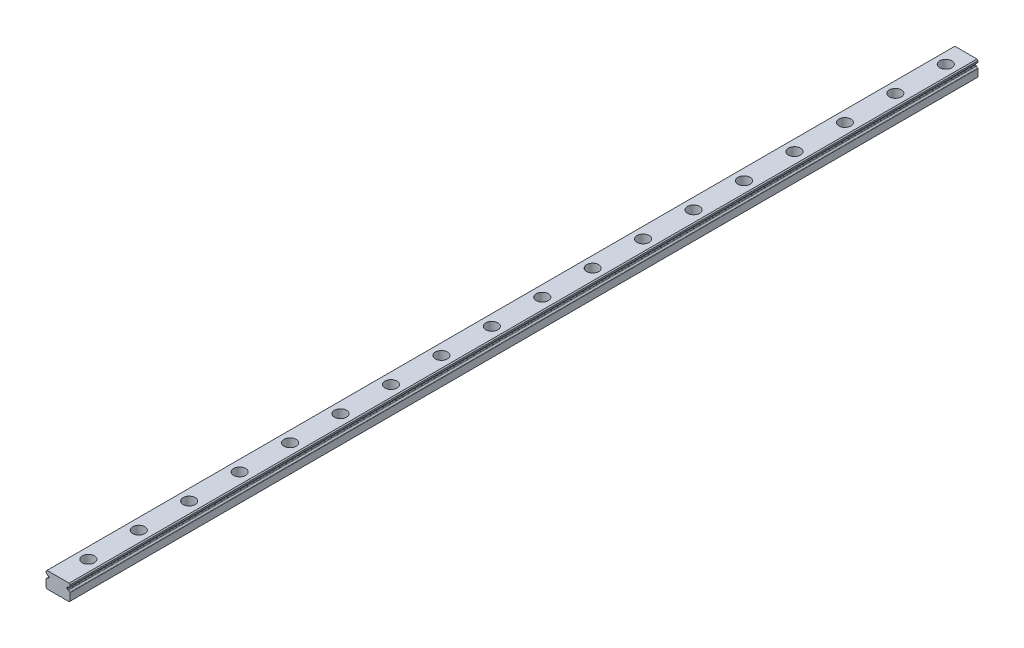
SolidWorks part; units mm, degrees
ref_plane "Płaszczyzna przednia" through (0, 0, 0) normal (0, 0, 1) x (1, 0, 0)
ref_plane "Płaszczyzna górna" through (0, 0, 0) normal (0, 1, 0) x (1, 0, 0)
ref_plane "Płaszczyzna prawa" through (0, 0, 0) normal (1, 0, 0) x (0, 0, -1)
ref_plane "Płaszczyzna1" through (0, 0, -250) normal (0, 0, -1) x (-1, 0, 0)
sketch "Szkic1" plane through (0, 0, -250) normal (0, 0, -1) x (-1, 0, 0)
  line L0 (4.4868, 0.454) -> (5.9823, 0.5848)
  line L1 (5.9823, 0.5848) -> (5.9823, 2.0015)
  line L2 (5.9823, 2.0015) -> (5.4838, 2.5)
  line L3 (5.4838, 2.5) -> (-5.4838, 2.5)
  line L4 (-5.4838, 2.5) -> (-5.9823, 2.0015)
  line L5 (-5.9823, 2.0015) -> (-5.9823, 0.5848)
  line L6 (-5.9823, 0.5848) -> (-4.4868, 0.454)
  line L7 (-4.4868, 0.454) -> (-4.4868, -0.454)
  line L8 (-4.4868, -0.454) -> (-5.9823, -0.5848)
  line L9 (-5.9823, -0.5848) -> (-5.9823, -5.5)
  line L10 (-5.9823, -5.5) -> (5.9823, -5.5)
  line L11 (5.9823, -5.5) -> (5.9823, -1.1747)
  line L12 (5.1943, -0.5159) -> (4.4868, -0.454)
  line L13 (4.4868, -0.454) -> (4.4868, 0.454)
  arc A0 (5.9823, -1.1747) -> (5.1943, -0.5159) centre (6.2815, -0.0162) cw
extrude "Dodanie-wyciągnięcie1" add sketch "Szkic1" against normal blind 450
sketch "Szkic2" plane through (0, 0, -250) normal (0, 0, -1) x (-1, 0, 0)
  line L0 (-2.3929, -5.5) -> (-1.5953, -5.5)
  arc A0 (-1.5953, -5.5) -> (-2.3929, -5.5) centre (-1.9941, -5.7991) ccw
extrude "Wytnij-wyciągnięcie1" cut sketch "Szkic2" against normal blind 500
sketch "Szkic3" plane through (0, 0, -250) normal (0, 0, -1) x (-1, 0, 0)
  line L0 (-5.1972, -0.5161) -> (-5.9823, -0.5848)
  line L1 (-5.9823, -0.5848) -> (-5.9823, -1.1927)
  arc A0 (-5.9823, -1.1927) -> (-5.1972, -0.5161) centre (-6.2938, -0.0375) ccw
extrude "Wytnij-wyciągnięcie2" cut sketch "Szkic3" against normal through all
sketch "Szkic4" plane through (0, 0, -250) normal (0, 0, -1) x (-1, 0, 0)
  line L0 (-5.9823, 1.1423) -> (-5.9823, 0.5848)
  line L1 (-5.9823, 0.5848) -> (-5.2105, 0.5173)
  arc A0 (-5.2105, 0.5173) -> (-5.9823, 1.1423) centre (-6.2815, -0.0162) ccw
extrude "Wytnij-wyciągnięcie3" cut sketch "Szkic4" against normal through all
sketch "Szkic5" plane through (0, 0, 200) normal (0, 0, 1) x (1, 0, 0)
  line L0 (-5.9823, 0.5848) -> (-5.2105, 0.5173)
  line L1 (-5.9823, 1.1423) -> (-5.9823, 0.5848)
  arc A0 (-5.2105, 0.5173) -> (-5.9823, 1.1423) centre (-6.2815, -0.0162) ccw
extrude "Wytnij-wyciągnięcie4" cut sketch "Szkic5" against normal through all
hole_wizard "Pogłębienie walcowe pod M3 Wkręt do części metalowych z łbem sześciokątnym1" positions "Szkic7" profile "Szkic6" counterbore size "M3" standard "Ansi Metric" end condition through all
sketch "Szkic7" plane through (0, 2.5, 0) normal (0, 1, 0) x (1, 0, 0)
  point P0 (0, 240)
  point P1 (0, -240)
  point P2 (0, 215)
  point P3 (0, 190)
  point P4 (0, 165)
  point P5 (0, 140)
  point P6 (0, 115)
  point P7 (0, 90)
  point P8 (0, 65)
  point P9 (0, 40)
  point P10 (0, 15)
  point P11 (0, -10)
  point P12 (0, -35)
  point P13 (0, -60)
  point P14 (0, -85)
  point P15 (0, -110)
  point P16 (0, -135)
  point P17 (0, -160)
  point P18 (0, -185)
  point P19 (0, -210)
sketch "Szkic6" plane through (0, 2.5, -240) normal (1, 0, 0) x (0, 0, 1)
  line L0 (0, 0) -> (0, 8)
  line L1 (0, 8) -> (1.75, 8)
  line L3 (1.75, 8) -> (1.75, 4.5)
  line L4 (1.75, 4.5) -> (3, 4.5)
  line L5 (3, 4.5) -> (3, 0)
  line L7 (3, 0) -> (0, 0)
  line L11 (0, -6.35) -> (0, 107.95) construction
  dimension "Średnica otworu na wylot" = 3.5
  dimension "Głębokość otworu na wylot" = 8
  dimension "Średnica pogłębienia walcowego" = 6
  dimension "Głębokość pogłębienia walcowego" = 4.5
chamfer "Sfazowanie1" distance 0.4985 angle 45 2 edges at (-5.9823, -5.5, -25) (5.9823, -5.5, -25)
fillet "Zaokrąglenie1" radius 0.2493 12 edges at (4.4868, -0.454, -25) (-5.9823, 1.1423, -25) (5.9823, -1.1927, -25) (-5.1943, -0.5159, -25) (4.4868, 0.454, -25) (-4.4868, -0.454, -25) (5.1972, -0.5161, -25) (-4.4868, 0.454, -25) (-5.9823, -1.1747, -25) (-5.2105, 0.5173, -25) (5.2105, 0.5173, -25) tangent propagation no
